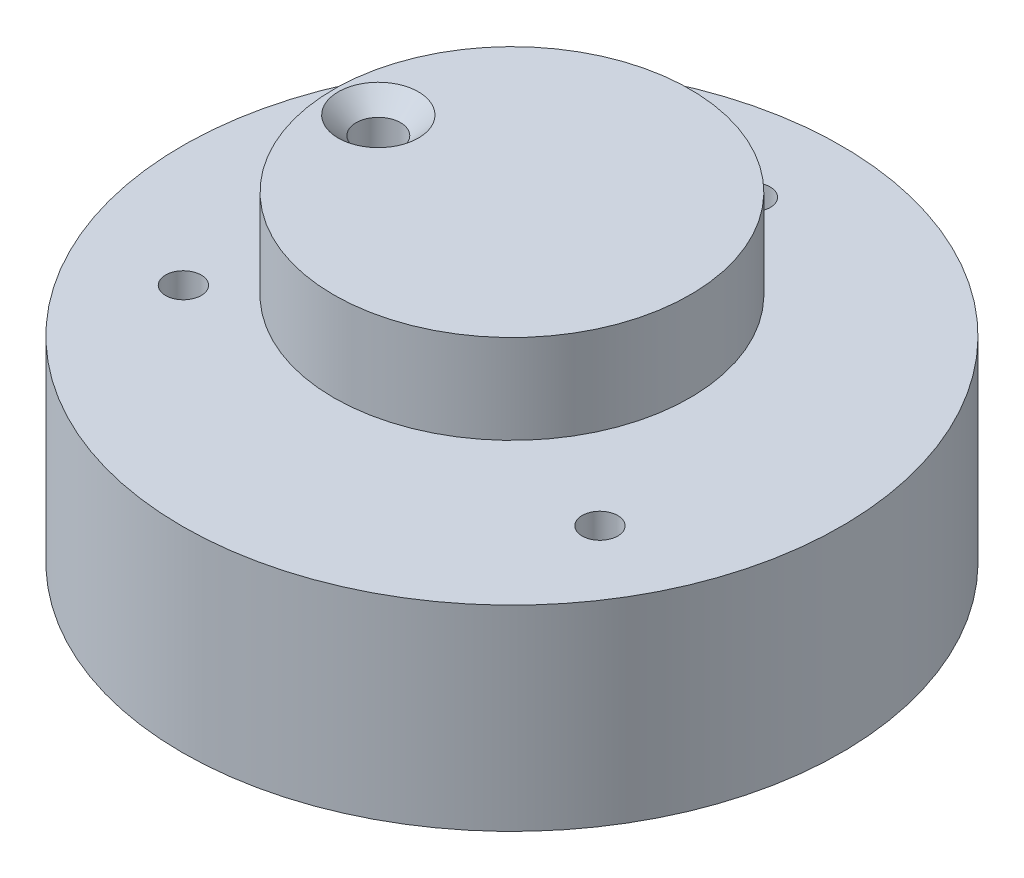
SolidWorks part; units mm, degrees
ref_plane "Front Plane" through (0, 0, 0) normal (0, 0, 1) x (1, 0, 0)
ref_plane "Top Plane" through (0, 0, 0) normal (0, 1, 0) x (1, 0, 0)
ref_plane "Right Plane" through (0, 0, 0) normal (1, 0, 0) x (0, 0, -1)
sketch "Sketch2" plane through (0, 0, 0) normal (0, 1, 0) x (1, 0, 0)
  line L0 (0, -13.5) -> (0, 13.5) construction
  line L1 (-11.6913, -6.75) -> (11.6913, 6.75) construction
  line L2 (-11.6913, 6.75) -> (11.6913, -6.75) construction
  circle A0 centre (0, 0) radius 18.5
  circle A1 centre (0, 13.5) radius 1
  circle A2 centre (0, -13.5) radius 1 construction
  circle A3 centre (-11.6913, 6.75) radius 1 construction
  circle A4 centre (-11.6913, -6.75) radius 1
  circle A5 centre (11.6913, -6.75) radius 1
  circle A6 centre (11.6913, 6.75) radius 1 construction
  circle A7 centre (0, 0) radius 13.5 construction
  point P6 (0, 0)
  point P11 (0, 0)
  point P14 (0, 0)
  dimension "D1" = 37
  dimension "D2" = 60
  dimension "D4" = 2
  dimension "D3" = 60
  dimension "D5" = 27
extrude "Boss-Extrude1" add sketch "Sketch2" along normal blind 11
sketch "Sketch4" plane through (0, 11, 0) normal (0, 1, 0) x (1, 0, 0)
  circle A0 centre (0, 0) radius 5
  dimension "D1" = 10
extrude "Boss-Extrude3" add sketch "Sketch4" along normal blind 2
sketch "Sketch5" plane through (0, 13, 0) normal (0, 1, 0) x (1, 0, 0)
  circle A0 centre (0, 0) radius 10
extrude "Boss-Extrude4" add sketch "Sketch5" along normal blind 5
sketch "Sketch6" plane through (0, 18, 0) normal (0, 1, 0) x (1, 0, 0)
  line L0 (-5, 0) -> (-10, 0) construction
  circle A0 centre (0, 0) radius 5 construction
  circle A1 centre (0, 0) radius 5 construction
  circle A2 centre (0, 0) radius 10 construction
  circle A3 centre (-7.5, 0) radius 1.25
  dimension "D1" = 2.5
extrude "Cut-Extrude1" cut sketch "Sketch6" against normal blind 5
chamfer "Chamfer1" distance 1 angle 45 1 edges at (-7.5, 18, 1.25)
fillet "Fillet1" radius 1 2 edges at (0, 13, 5) (0, 11, 5)
